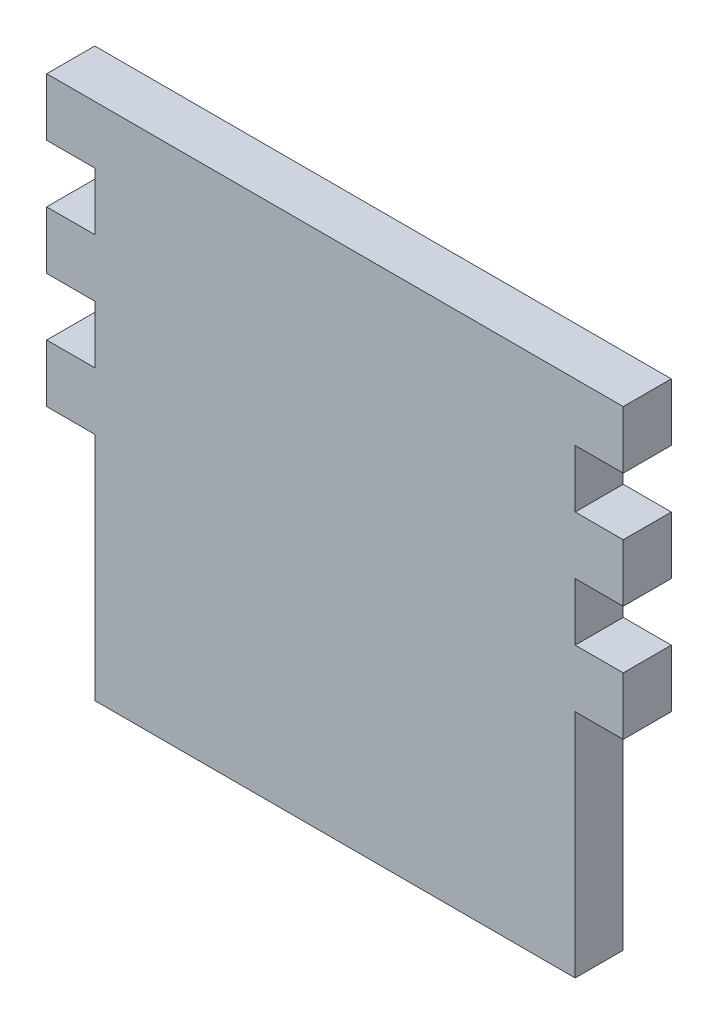
SolidWorks part; units mm, degrees
ref_plane "Front Plane" through (0, 0, 0) normal (0, 0, 1) x (1, 0, 0)
ref_plane "Top Plane" through (0, 0, 0) normal (0, 1, 0) x (1, 0, 0)
ref_plane "Right Plane" through (0, 0, 0) normal (1, 0, 0) x (0, 0, -1)
sketch "Sketch1" plane through (0, 0, 0) normal (0, 0, 1) x (1, 0, 0)
  line L1 (-37.8801, 17.0433) -> (38.3199, 17.0433)
  line L2 (-37.8801, 17.0433) -> (-37.8801, -59.1567)
  line L3 (-37.8801, -59.1567) -> (38.3199, -59.1567)
  line L4 (38.3199, 17.0433) -> (38.3199, -59.1567)
  dimension "D1" = 76.2
  dimension "D2" = 76.2
extrude "Boss-Extrude1" add sketch "Sketch1" along normal blind 6.35
sketch "Sketch2" plane through (0, 0, 6.35) normal (0, 0, 1) x (1, 0, 0)
  line L0 (-37.8801, 17.0433) -> (-31.5301, 17.0433)
  line L1 (38.3199, 17.0433) -> (-37.8801, 17.0433) construction
  line L2 (-31.5301, 17.0433) -> (-31.5301, 9.4233)
  line L3 (-31.5301, 9.4233) -> (-37.8801, 9.4233)
  line L4 (-37.8801, 17.0433) -> (-37.8801, -59.1567) construction
  line L5 (-37.8801, 9.4233) -> (-37.8801, 1.8033)
  line L6 (-37.8801, 1.8033) -> (-31.5301, 1.8033)
  line L7 (-31.5301, 1.8033) -> (-31.5301, -5.8167)
  line L8 (-31.5301, -5.8167) -> (-37.8801, -5.8167)
  line L9 (-37.8801, -5.8167) -> (-37.8801, -13.4367)
  line L10 (-37.8801, -13.4367) -> (-31.5301, -13.4367)
  line L11 (-31.5301, -13.4367) -> (-31.5301, -21.0567)
  line L12 (-31.5301, -21.0567) -> (-37.8801, -21.0567)
  line L13 (-37.8801, -21.0567) -> (-46.7258, -21.0567)
  line L14 (-37.8801, -21.0567) -> (-37.8801, -28.6767) [skipped]
  line L15 (-46.7258, -21.0567) -> (-46.7258, 17.0433)
  line L16 (-46.7258, 17.0433) -> (-37.8801, 17.0433)
  line L19 (47.1657, -21.0567) -> (47.1657, 17.0433)
  line L20 (38.3199, -21.0567) -> (47.1657, -21.0567)
  line L21 (31.9699, -21.0567) -> (38.3199, -21.0567)
  line L22 (31.9699, -13.4367) -> (31.9699, -21.0567)
  line L23 (38.3199, -13.4367) -> (31.9699, -13.4367)
  line L24 (38.3199, -5.8167) -> (38.3199, -13.4367)
  line L25 (31.9699, -5.8167) -> (38.3199, -5.8167)
  line L26 (31.9699, 1.8033) -> (31.9699, -5.8167)
  line L27 (38.3199, 1.8033) -> (31.9699, 1.8033)
  line L28 (38.3199, 9.4233) -> (38.3199, 1.8033)
  line L29 (31.9699, 9.4233) -> (38.3199, 9.4233)
  line L30 (31.9699, 17.0433) -> (31.9699, 9.4233)
  line L31 (38.3199, 17.0433) -> (31.9699, 17.0433)
  line L32 (47.1657, 17.0433) -> (38.3199, 17.0433)
  dimension "D1" = 7.62
  dimension "D2" = 7.62
  dimension "D3" = 6.35
  dimension "D4" = 6.35
  dimension "D6" = 38.1
  dimension "D5" = 3
extrude "Cut-Extrude1" cut sketch "Sketch2" against normal blind 6.35
sketch "Sketch3" plane through (0, 0, 6.35) normal (0, 0, 1) x (1, 0, 0)
  line L1 (-31.5301, -21.0567) -> (-37.8801, -21.0567)
  line L2 (-31.5301, -21.0567) -> (-31.5301, -59.1567)
  line L3 (-31.5301, -59.1567) -> (-37.8801, -59.1567)
  line L4 (-37.8801, -21.0567) -> (-37.8801, -59.1567)
  line L5 (31.9699, -21.0567) -> (38.3199, -21.0567)
  line L6 (31.9699, -21.0567) -> (31.9699, -59.1567)
  line L7 (31.9699, -59.1567) -> (38.3199, -59.1567)
  line L8 (38.3199, -21.0567) -> (38.3199, -59.1567)
extrude "Cut-Extrude2" cut sketch "Sketch3" against normal blind 6.35
sketch "Sketch4" plane through (0, 0, 6.35) normal (0, 0, 1) x (1, 0, 0)
  line L0 (-31.5301, -13.4367) -> (-31.5301, -21.0567)
  line L1 (-31.5301, -59.1567) -> (-31.5301, -13.4367) construction
  line L2 (-31.5301, -21.0567) -> (-37.8801, -21.0567)
  line L3 (-37.8801, -21.0567) -> (-37.8801, -28.6767)
  line L4 (-37.8801, -28.6767) -> (-31.5301, -28.6767)
  line L5 (-31.5301, -21.0567) -> (-31.5301, -28.6767)
  line L6 (0.2199, 17.0433) -> (0.2199, -59.1567)
  line L7 (31.9699, 17.0433) -> (-31.5301, 17.0433) construction
  line L8 (-31.5301, -59.1567) -> (31.9699, -59.1567) construction
  line L9 (31.9699, -21.0567) -> (38.3199, -21.0567)
  line L10 (38.3199, -21.0567) -> (38.3199, -28.6767)
  line L11 (38.3199, -28.6767) -> (31.9699, -28.6767)
  line L12 (31.9699, -21.0567) -> (31.9699, -28.6767)
  line M6 (-31.5301, -13.4367) -> (-31.5301, -59.1567)
  line M8 (31.9699, -59.1567) -> (31.9699, -13.4367)
  dimension "D1" = 7.62
  dimension "D2" = 7.62
  dimension "D3" = 6.35
  dimension "D4" = 6.35
extrude "Boss-Extrude3" add sketch "Sketch4" against normal blind 6.35 contours L3 L4 L2 M6 | L11 L10 L9 M8 region at (-34.7051, -24.8667, 6.35) region at (35.1449, -24.8667, 6.35)
sketch "Sketch5" plane through (0, 17.0433, 0) normal (0, 1, 0) x (1, 0, 0)
  line L1 (-31.5301, 0) -> (31.9699, 0)
  line L2 (-31.5301, 0) -> (-31.5301, -6.35)
  line L3 (-31.5301, -6.35) -> (31.9699, -6.35)
  line L4 (31.9699, 0) -> (31.9699, -6.35)
extrude "Cut-Extrude3" cut sketch "Sketch5" against normal blind 7.62
